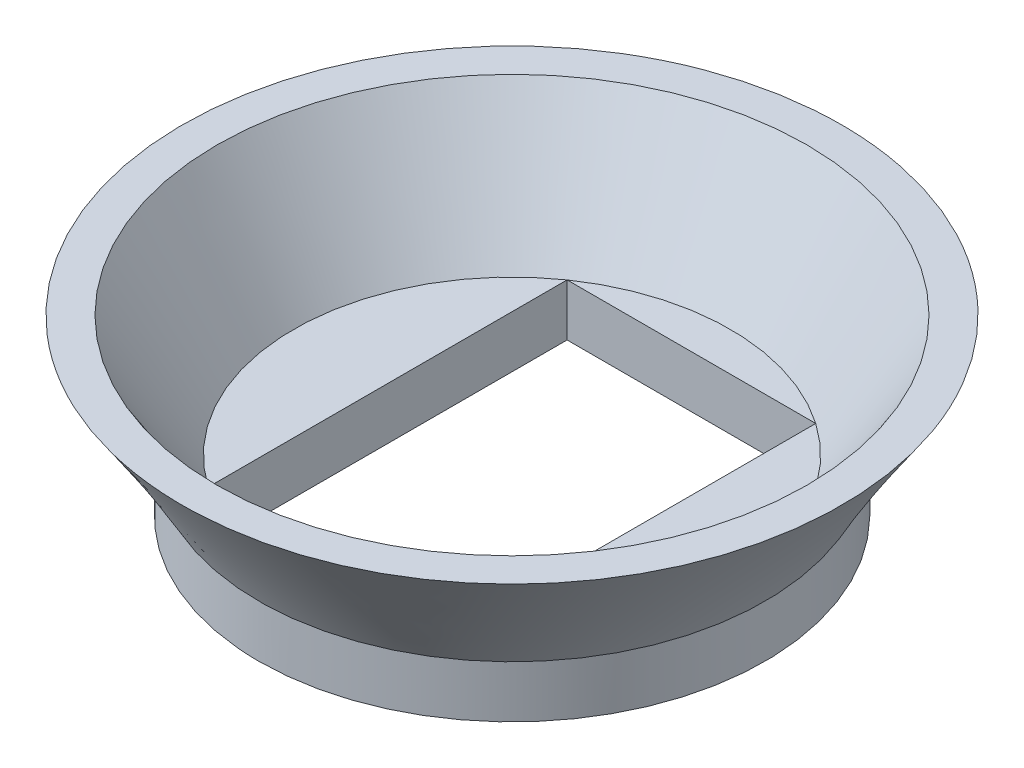
SolidWorks part; units mm, degrees
ref_plane "Front Plane" through (0, 0, 0) normal (0, 0, 1) x (1, 0, 0)
ref_plane "Top Plane" through (0, 0, 0) normal (0, 1, 0) x (1, 0, 0)
ref_plane "Right Plane" through (0, 0, 0) normal (1, 0, 0) x (0, 0, -1)
sketch "Sketch1" plane through (0, 0, 0) normal (0, 1, 0) x (1, 0, 0)
  circle A0 centre (0, 0) radius 8.75
  dimension "D1" = 17.5
extrude "Boss-Extrude1" add sketch "Sketch1" along normal blind 1.8
sketch "Sketch2" plane through (0, 1.8, 0) normal (0, 1, 0) x (1, 0, 0)
  circle A0 centre (0, 0) radius 8.75
  circle A1 centre (0, 0) radius 7.55
  circle A2 centre (0, 0) radius 8.75 construction
  dimension "D1" = 1.2
ref_plane "Plane1" through (0, 6, 0) normal (0, 1, 0) x (1, 0, 0)
sketch "Sketch3" plane through (0, 6, 0) normal (0, 1, 0) x (1, 0, 0)
  circle A0 centre (0, 0) radius 11.4
  circle A1 centre (0, 0) radius 10.2
  dimension "D1" = 22.8
  dimension "D2" = 20.4
loft "Loft1" add section "Sketch2" section "Sketch3" connector at (-0.7577, 1.8, 8.7171) connector at (-3.8144, 6, 10.7429)
loft "Cut-Loft1" cut section "Sketch2<76>" section "Sketch3<51>" connector at (-0.493, 1.8, 7.5339) connector at (-2.1123, 6, 9.9789)
sketch "Sketch2<76>" plane through (0, 1.8, 0) normal (0, 1, 0) x (1, 0, 0) same geometry as "Sketch2"
sketch "Sketch3<51>" plane through (0, 6, 0) normal (0, 1, 0) x (1, 0, 0) same geometry as "Sketch3"
sketch "Sketch4" plane through (0, 1.8, 0) normal (0, 1, 0) x (1, 0, 0)
  line L1 (4.3, 6.2058) -> (-4.3, 6.2058)
  line L2 (4.3, 6.2058) -> (4.3, -6.2058)
  line L3 (4.3, -6.2058) -> (-4.3, -6.2058)
  line L4 (-4.3, 6.2058) -> (-4.3, -6.2058)
  line L5 (4.3, 6.2058) -> (-4.3, -6.2058) construction
  line L6 (4.3, -6.2058) -> (-4.3, 6.2058) construction
  circle A0 centre (0, 0) radius 7.55 construction
  point P0 (0, 0)
  dimension "D1" = 8.6
extrude "Cut-Extrude1" cut sketch "Sketch4" against normal through all
